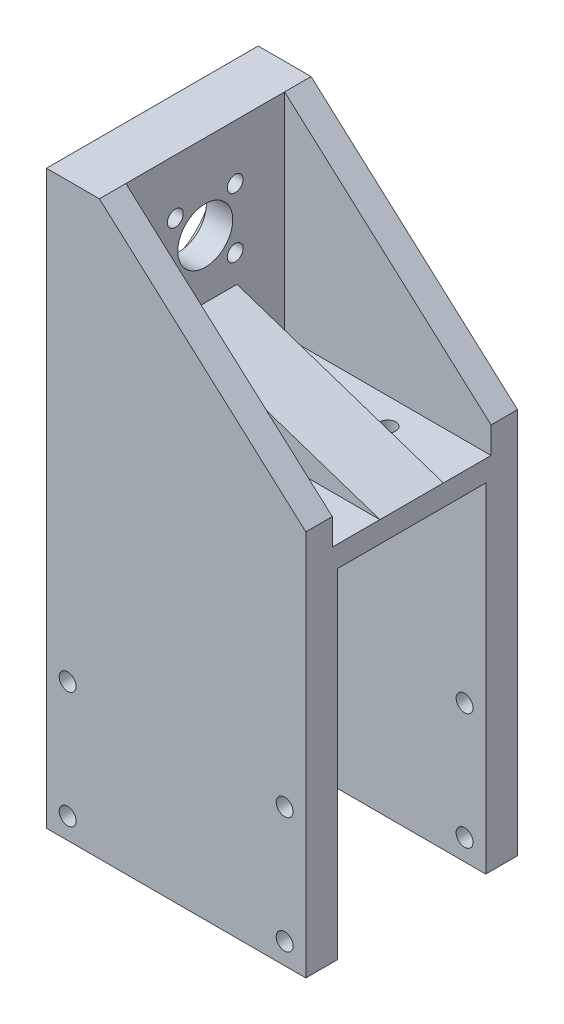
SolidWorks part; units mm, degrees
ref_plane "前视基准面" through (0, 0, 0) normal (0, 0, 1) x (1, 0, 0)
ref_plane "上视基准面" through (0, 0, 0) normal (0, 1, 0) x (1, 0, 0)
ref_plane "右视基准面" through (0, 0, 0) normal (1, 0, 0) x (0, 0, -1)
other "Configuration Table"
sketch "草图1" plane through (0, 0, 0) normal (0, 1, 0) x (1, 0, 0)
  line L1 (-24.5, -20) -> (24.5, -20)
  line L2 (-24.5, -20) -> (-24.5, 20)
  line L3 (-24.5, 20) -> (24.5, 20)
  line L4 (24.5, -20) -> (24.5, 20)
  line L5 (-24.5, -20) -> (24.5, 20) construction
  line L6 (-24.5, 20) -> (24.5, -20) construction
  point P0 (0, 0)
  dimension "D1" = 49
  dimension "D2" = 40
extrude "凸台-拉伸1" add sketch "草图1" along normal blind 4
sketch "草图2" plane through (0, 4, 0) normal (0, 1, 0) x (1, 0, 0)
  line L0 (0, 20) -> (0, -20) construction
  line L1 (24.5, 20) -> (-24.5, 20) construction
  line L2 (-24.5, -20) -> (24.5, -20) construction
  line L3 (-24.5, 0) -> (24.5, 0) construction
  line L4 (-24.5, 20) -> (-24.5, -20) construction
  line L5 (24.5, -20) -> (24.5, 20) construction
  circle A0 centre (-10, 10) radius 1.5
  circle A1 centre (10, 10) radius 1.5
  circle A2 centre (10, -10) radius 1.5
  circle A3 centre (-10, -10) radius 1.5
  point P20 (0, 0)
  point P21 (0, 0)
  point P22 (0, 0)
  dimension "D1" = 3
  dimension "D2" = 3
  dimension "D3" = 3
  dimension "D4" = 3
  dimension "D5" = 20
  dimension "D6" = 20
extrude "切除-拉伸1" cut sketch "草图2" against normal through all
sketch "草图3" plane through (0, 4, 0) normal (0, 1, 0) x (1, 0, 0)
  line L5 (-24.5, 0) -> (24.5, 0) construction
  line L6 (-24.5, 20) -> (-24.5, -20) construction
  line L7 (24.5, -20) -> (24.5, 20) construction
  line L9 (-24.5, 15) -> (-14.5, 15)
  line L10 (-24.5, 15) -> (-24.5, -15)
  line L11 (-24.5, -15) -> (-14.5, -15)
  line L12 (-14.5, 15) -> (-14.5, -15)
  dimension "D1" = 10
  dimension "D2" = 30
extrude "凸台-拉伸3" add sketch "草图3" along normal blind 40
sketch "草图4" plane through (-24.5, 0, 0) normal (-1, 0, 0) x (0, 0, 1)
  line L0 (0, 44) -> (0, 0) construction
  line L1 (-15, 44) -> (15, 44) construction
  line L2 (15, 4) -> (20, 4) construction
  circle A0 centre (0, 28) radius 5.2
  dimension "D1" = 10.4
  dimension "D2" = 24
extrude "切除-拉伸2" cut sketch "草图4" against normal through all
sketch "草图5" plane through (-24.5, 0, 0) normal (-1, 0, 0) x (0, 0, 1)
  circle A0 centre (0, 28) radius 11.75
  dimension "D1" = 23.5
extrude "切除-拉伸3" cut sketch "草图5" against normal blind 5
sketch "草图6" plane through (-19.5, 0, 0) normal (-1, 0, 0) x (0, 0, 1)
  line L1 (-5.6569, 22.3431) -> (5.6569, 22.3431) construction
  line L2 (-5.6569, 22.3431) -> (-5.6569, 33.6569) construction
  line L3 (-5.6569, 33.6569) -> (5.6569, 33.6569) construction
  line L4 (5.6569, 22.3431) -> (5.6569, 33.6569) construction
  line L5 (-5.6569, 22.3431) -> (5.6569, 33.6569) construction
  line L6 (-5.6569, 33.6569) -> (5.6569, 22.3431) construction
  circle A0 centre (0, 28) radius 8 construction
  circle A1 centre (-5.6569, 33.6569) radius 1.5
  circle A2 centre (5.6569, 33.6569) radius 1.5
  circle A3 centre (5.6569, 22.3431) radius 1.5
  circle A4 centre (-5.6569, 22.3431) radius 1.5
  dimension "D1" = 16
  dimension "D2" = 3
  dimension "D3" = 3
  dimension "D4" = 3
  dimension "D5" = 3
extrude "切除-拉伸4" cut sketch "草图6" against normal through all
ref_plane "基准面2" through (0, 0, 0) normal (0, 0, -1) x (-1, 0, 0)
sketch "草图7" plane through (0, 0, 0) normal (0, 0, -1) x (-1, 0, 0)
  line L0 (14.5, 17) -> (-24.5, 4)
  line L1 (14.5, 44) -> (14.5, 4) construction
  line L2 (-24.5, 4) -> (14.5, 4)
  line L3 (14.5, 4) -> (14.5, 17)
  dimension "D1" = 13
extrude "凸台-拉伸4" add sketch "草图7" along normal mid plane 12
sketch "草图8" plane through (-24.5, 0, 0) normal (-1, 0, 0) x (0, 0, 1)
  line L1 (20, 0) -> (14, 0)
  line L2 (20, 0) -> (20, -64)
  line L3 (20, -64) -> (14, -64)
  line L4 (14, 0) -> (14, -64)
  line L5 (-20, 0) -> (-14, 0)
  line L6 (-20, 0) -> (-20, -64)
  line L7 (-20, -64) -> (-14, -64)
  line L8 (-14, 0) -> (-14, -64)
  dimension "D1" = 6
  dimension "D2" = 6
  dimension "D3" = 64
  dimension "D4" = 64
extrude "凸台-拉伸5" add sketch "草图8" against normal up to surface (49 mm away) up to face at (24.5, 2.6667, 0)
sketch "草图9" plane through (0, 0, 20) normal (0, 0, 1) x (1, 0, 0)
  line L0 (24.5, 4) -> (24.5, -64) construction
  line L1 (24.5, -64) -> (-24.5, -64) construction
  line L2 (-24.5, 4) -> (-24.5, -64) construction
  circle A0 centre (20.5, -60) radius 1.6
  circle A1 centre (-20.5, -60) radius 1.6
  circle A2 centre (20.5, -38) radius 1.6
  circle A3 centre (-20.5, -38) radius 1.6
  dimension "D1" = 3.2
  dimension "D2" = 3.2
  dimension "D3" = 3.2
  dimension "D4" = 3.2
  dimension "D5" = 4
  dimension "D6" = 4
  dimension "D7" = 4
  dimension "D8" = 4
  dimension "D9" = 4
  dimension "D10" = 26
  dimension "D11" = 4
  dimension "D12" = 26
extrude "切除-拉伸5" cut sketch "草图9" against normal through all
sketch "草图11" plane through (0, 0, 15) normal (0, 0, 1) x (1, 0, 0)
  line L0 (-14.5, 44) -> (24.5, 9)
  line L1 (-24.5, 4) -> (-14.5, 4)
  line L2 (-24.5, 4) -> (-24.5, 44)
  line L3 (-24.5, 44) -> (-14.5, 44)
  line L5 (24.5, 9) -> (24.5, 4)
  line L6 (24.5, 4) -> (-14.5, 4)
  dimension "D1" = 5
extrude "凸台-拉伸6" add sketch "草图11" along normal blind 5
mirror "镜向2" about plane through (0, 0, 0) normal (0, 0, -1) of "凸台-拉伸6"
